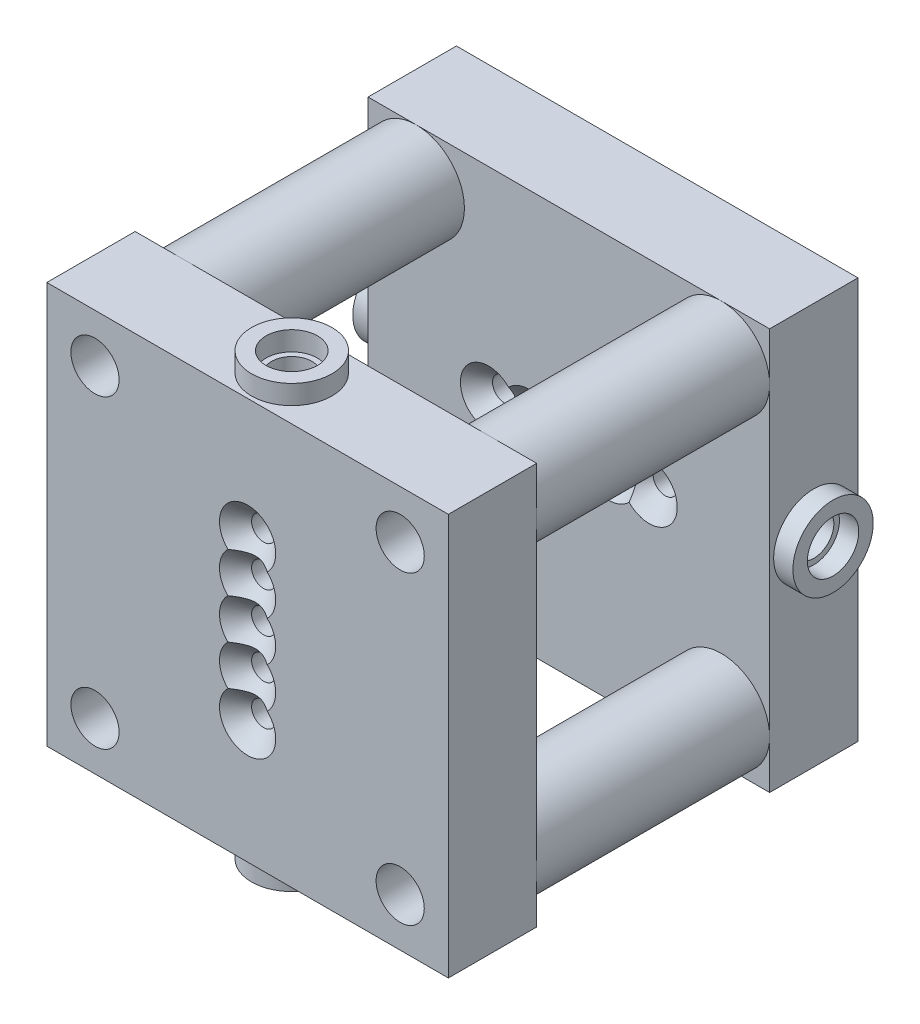
SolidWorks part; units mm, degrees
material "ﾎﾟﾘｵｷｼﾒﾁﾚﾝ(POM)ｱｾﾀｰﾙ共重合体"
ref_plane "正面" through (0, 0, 0) normal (0, 0, 1) x (1, 0, 0)
ref_plane "平面" through (0, 0, 0) normal (0, 1, 0) x (1, 0, 0)
ref_plane "右側面" through (0, 0, 0) normal (1, 0, 0) x (0, 0, -1)
sketch "ｽｹｯﾁ1" plane through (0, 0, 0) normal (0, 0, 1) x (1, 0, 0)
  line L0 (0, 0) -> (0, -12.5) construction
  line L1 (-12.5, 12.5) -> (12.5, 12.5)
  line L2 (-12.5, 12.5) -> (-12.5, -12.5)
  line L3 (-12.5, -12.5) -> (12.5, -12.5)
  line L4 (12.5, 12.5) -> (12.5, -12.5)
  line L5 (-12.5, 12.5) -> (12.5, -12.5) construction
  line L6 (-12.5, -12.5) -> (12.5, 12.5) construction
  circle A0 centre (0, 0) radius 0.75
  circle A1 centre (2.5, 0) radius 0.75
  circle A2 centre (5, 0) radius 0.75
  circle A3 centre (-5, 0) radius 0.75
  circle A4 centre (-2.5, 0) radius 0.75
  point P0 (0, 0)
  dimension "D2" = 1.5
  dimension "D1" = 25
  dimension "D4" = 10
  dimension "D3" = 3
extrude "ﾎﾞｽ - 押し出し1" add sketch "ｽｹｯﾁ1" along normal blind 5.5
hole_wizard "M3x0.5 ねじ穴1" positions "ｽｹｯﾁ15" profile "ｽｹｯﾁ16" tap size "M3x0.5" standard "JIS"
sketch "ｽｹｯﾁ15" plane through (-12.5, 0, 0) normal (-1, 0, 0) x (0, 0, 1)
  line L0 (2.75, -12.5) -> (2.75, 0) construction
  line L1 (5.5, -12.5) -> (0, -12.5) construction
  line L2 (2.75, 0) -> (0, 0) construction
  line L3 (0, 12.5) -> (0, -12.5) construction
  point P0 (2.75, 0)
sketch "ｽｹｯﾁ16" plane through (-12.5, 0, 2.75) normal (0, 1, 0) x (0, 0, 1)
  line L0 (0, 0) -> (0, 5.7511)
  line L1 (0, 5.7511) -> (1.25, 5)
  line L2 (1.25, 5) -> (1.25, 0)
  line L5 (1.25, 0) -> (0, 0)
  line L10 (0, 5.7511) -> (-1.25, 5) construction
  line L11 (0, -6.35) -> (0, 107.95) construction
  dimension "ねじ下穴ﾄﾞﾘﾙ直径" = 2.5
  dimension "ねじ下穴ﾄﾞﾘﾙの深さ" = 5
  dimension "ﾄﾞﾘﾙ角度" = 118
cosmetic thread "穴のねじ山1" parameters "D1"=6, "D2"=3
sketch "ｽｹｯﾁ17" plane through (-12.5, 0, 0) normal (-1, 0, 0) x (0, 0, 1)
  circle A0 centre (2.75, 0) radius 1.6
  circle A1 centre (2.75, 0) radius 2.5
  dimension "D1" = 3.2
  dimension "D2" = 5
extrude "ﾎﾞｽ - 押し出し3" add sketch "ｽｹｯﾁ17" along normal blind 1.2 separate body
chamfer "面取り1" distance 1 angle 45 10 edges at (5.75, 0, 5.5) (3.25, 0, 5.5) (0.75, 0, 5.5) (-3.25, 0, 5.5) (-5.75, 0, 5.5) (-5.75, 0, 0) (-3.25, 0, 0) (0.75, 0, 0) (3.25, 0, 0) (5.75, 0, 0)
mirror "ﾐﾗｰ1" about plane through (0, 0, 0) normal (1, 0, 0) of "M3x0.5 ねじ穴1"
mirror "ﾐﾗｰ2" about plane through (0, 0, 0) normal (1, 0, 0) of bodies 113
pattern_linear "直線ﾊﾟﾀｰﾝ1" count 2 spacing 20 along (0, 0, 1) of bodies 116 113 112 101
move or copy body "ﾎﾞﾃﾞｨ-移動/ｺﾋﾟｰ1" bodies to move or copy 102 117 118 copy no rotation origin (0, 0, 0) rotation axis (0, 0, 1) rotation angle 90
hole_wizard "M3 すきま穴1" positions "ｽｹｯﾁ2" profile "ｽｹｯﾁ3" hole size "M3" standard "JIS" end condition through all
sketch "ｽｹｯﾁ2" plane through (0, 0, 25.5) normal (0, 0, 1) x (1, 0, 0)
  line L1 (-9.5, 9.5) -> (9.5, 9.5)
  line L2 (-9.5, 9.5) -> (-9.5, -9.5)
  line L3 (-9.5, -9.5) -> (9.5, -9.5)
  line L4 (9.5, 9.5) -> (9.5, -9.5)
  line L5 (-9.5, 9.5) -> (9.5, -9.5) construction
  line L7 (12.5, 12.5) -> (-12.5, 12.5) construction
  point P0 (9.5, 9.5)
  point P2 (9.5, -9.5)
  point P4 (-9.5, -9.5)
  point P6 (-9.5, 9.5)
  dimension "D1" = 3
sketch "ｽｹｯﾁ3" plane through (9.5, 9.5, 25.5) normal (1, 0, 0) x (0, -1, 0)
  line L0 (0, 0) -> (0, 25.7429)
  line L1 (0, 25.7429) -> (1.5, 25.7429)
  line L2 (1.5, 25.7429) -> (1.5, 0)
  line L5 (1.5, 0) -> (0, 0)
  line L11 (0, -6.35) -> (0, 107.95) construction
  dimension "通し穴の直径" = 3
  dimension "通し穴の深さ" = 25.7429
sketch "ｽｹｯﾁ4" plane through (0, 0, 5.5) normal (0, 0, 1) x (1, 0, 0)
  circle A0 centre (9.5, 9.5) radius 1.5 construction
  circle A1 centre (9.5, -9.5) radius 1.5 construction
  circle A2 centre (-9.5, -9.5) radius 1.5 construction
  circle A3 centre (-9.5, 9.5) radius 1.5 construction
  circle A4 centre (9.5, 9.5) radius 1.5
  circle A5 centre (9.5, -9.5) radius 1.5
  circle A6 centre (-9.5, -9.5) radius 1.5
  circle A7 centre (-9.5, 9.5) radius 1.5
  circle A8 centre (9.5, 9.5) radius 3
  circle A9 centre (9.5, -9.5) radius 3
  circle A10 centre (-9.5, -9.5) radius 3
  circle A11 centre (-9.5, 9.5) radius 3
  dimension "D1" = 1.5
extrude "ﾎﾞｽ - 押し出し2" add sketch "ｽｹｯﾁ4" along normal up to surface (14.5 mm away) separate body up to face at (11, 9.5, 20)
sketch3d "3Dｽｹｯﾁ1"
  line L0 (-5, 0, 5.5) -> (0, -5, 20)
  line L1 (-5, 0, 4.5) -> (-5, 0, 1) construction
  line L2 (0, -5, 24.5) -> (0, -5, 21) construction
  line L3 (-2.5, 0, 5.5) -> (0, -2.5, 20)
  line L4 (-2.5, 0, 4.5) -> (-2.5, 0, 1) construction
  line L5 (0, -2.5, 24.5) -> (0, -2.5, 21) construction
  line L6 (0, 0, 5.5) -> (0, 0, 20)
  line L7 (0, 0, 4.5) -> (0, 0, 1) construction
  line L8 (0, 0, 24.5) -> (0, 0, 21) construction
  line L9 (2.5, 0, 5.5) -> (0, 2.5, 20)
  line L10 (2.5, 0, 4.5) -> (2.5, 0, 1) construction
  line L11 (0, 2.5, 24.5) -> (0, 2.5, 21) construction
  line L12 (5, 0, 5.5) -> (0, 5, 20)
  line L13 (5, 0, 4.5) -> (5, 0, 1) construction
  line L14 (0, 5, 24.5) -> (0, 5, 21) construction
sketch "ｽｹｯﾁ18" plane through (0, 0, 0) normal (1, 0, 0) x (0, 0, -1)
  line L0 (-20, 5) -> (-22.75, 5)
  line L1 (-25.5, 12.5) -> (-20, 12.5) construction
  line L2 (-20, 2.5) -> (-22.75, 2.5)
  line L3 (-20, 0) -> (-22.75, 0)
  line L4 (-20, -2.5) -> (-22.75, -2.5)
  line L5 (-20, -5) -> (-22.75, -5)
  point P6 (-22.75, 12.5)
  dimension "D1" = 5
sketch "ｽｹｯﾁ19" plane through (0, 0, 0) normal (0, 1, 0) x (1, 0, 0)
  line L0 (-5, -5.5) -> (-5, -2.75)
  line L1 (-2.5, -5.5) -> (-2.5, -2.75)
  line L2 (0, -5.5) -> (0, -2.75)
  line L3 (2.5, -5.5) -> (2.5, -2.75)
  line L4 (5, -5.5) -> (5, -2.75)
  line L5 (12.5, -5.5) -> (-12.5, -5.5) construction
  line L6 (5, -5.5) -> (0, -20) construction
  dimension "D1" = 5
